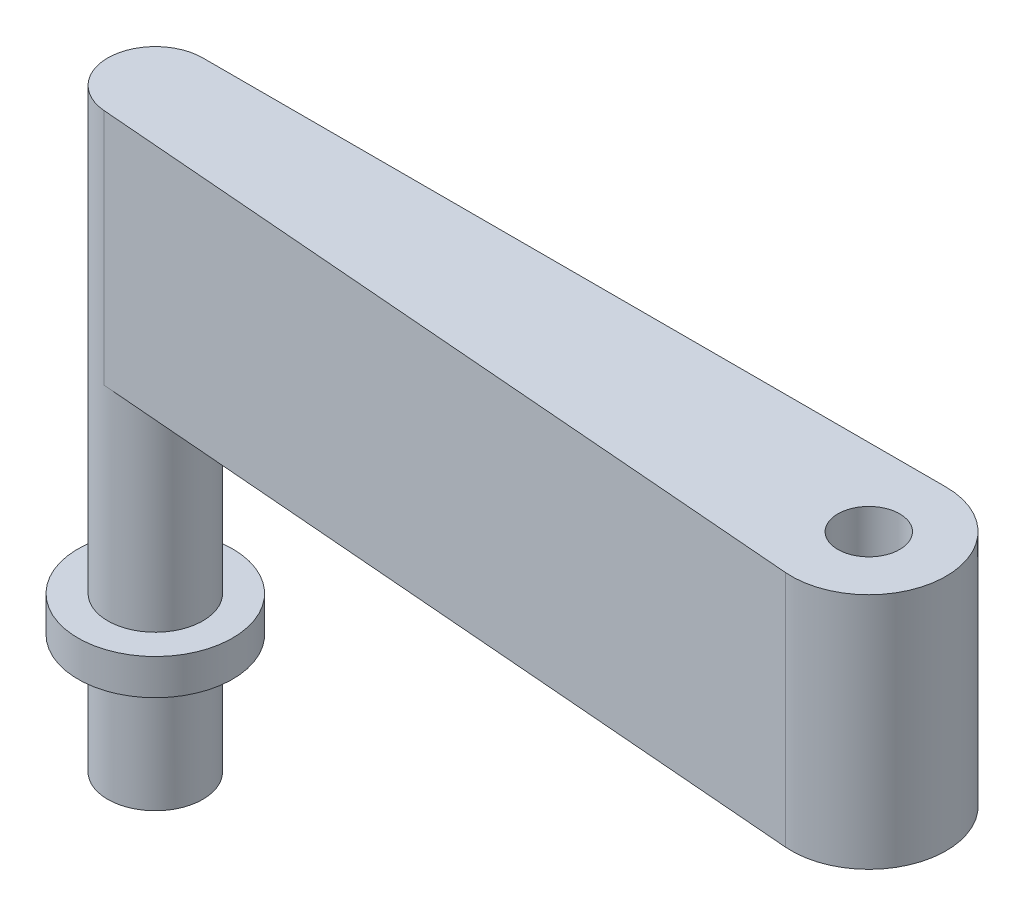
SolidWorks part; units mm, degrees
ref_plane "Alzado" through (0, 0, 0) normal (0, 0, 1) x (1, 0, 0)
ref_plane "Planta" through (0, 0, 0) normal (0, 1, 0) x (1, 0, 0)
ref_plane "Vista lateral" through (0, 0, 0) normal (1, 0, 0) x (0, 0, -1)
sketch "Croquis1" plane through (0, 0, 0) normal (0, 1, 0) x (1, 0, 0)
  line L0 (-62.5, 6.5) -> (0, 6.5)
  line L2 (0, 15.0922) -> (0, -13.2624) construction
  line L3 (70.9164, 0) -> (-21.8302, 0) construction
  line L4 (-62.8195, -1.4872) -> (-0.5192, -6.4792)
  arc A0 (-62.5, 6.5) -> (-62.8195, -1.4872) centre (-62.5, 2.5) ccw
  arc A2 (-0.5192, -6.4792) -> (0, 6.5) centre (0, 0) ccw
  dimension "D1" = 13
  dimension "D2" = 4
  dimension "D4" = 73
extrude "Saliente-Extruir1" add sketch "Croquis1" along normal mid plane 20
sketch "Croquis2" plane through (0, 10, 0) normal (0, 1, 0) x (1, 0, 0)
  circle A0 centre (0, 0) radius 2.6
  dimension "D1" = 5.2
extrude "Cortar-Extruir1" cut sketch "Croquis2" against normal through all
sketch "Croquis3" plane through (0, -10, 0) normal (0, 1, 0) x (1, 0, 0)
  circle A0 centre (-62.5, 2.5) radius 4
  arc A1 (-62.5, 6.5) -> (-62.8195, -1.4872) centre (-62.5, 2.5) ccw construction
extrude "Saliente-Extruir2" add sketch "Croquis3" against normal blind 30
sketch "Croquis4" plane through (0, -40, 0) normal (0, -1, 0) x (-1, 0, 0)
  circle A0 centre (62.5, 2.5) radius 2.6
  dimension "D1" = 5.2
extrude "Cortar-Extruir2" cut sketch "Croquis4" against normal blind 10 contours A0
sketch "Croquis5" plane through (0, -40, 0) normal (0, -1, 0) x (1, 0, 0)
  circle A0 centre (-62.5, -2.5) radius 4
  circle A1 centre (-62.5, -2.5) radius 6.5
  dimension "D1" = 2.5
  dimension "D2" = 8
extrude "Saliente-Extruir3" add sketch "Croquis5" along normal blind 3 from offset 13 offset against normal yes
